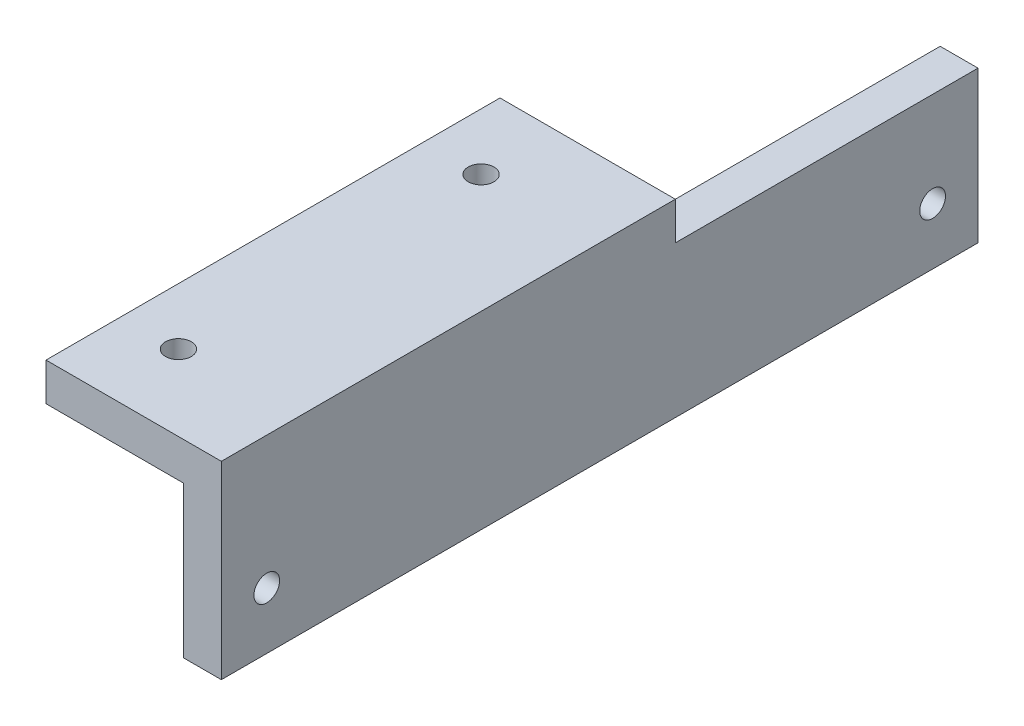
SolidWorks part; units mm, degrees
ref_plane "Front" through (0, 0, 0) normal (0, 0, 1) x (1, 0, 0)
ref_plane "Top" through (0, 0, 0) normal (0, 1, 0) x (1, 0, 0)
ref_plane "Right" through (0, 0, 0) normal (1, 0, 0) x (0, 0, -1)
sketch "Sketch1" plane through (0, 0, 0) normal (1, 0, 0) x (0, 0, -1)
  line L0 (50, 20) -> (50, 0)
  line L1 (0, 0) -> (100, 0)
  line L2 (0, 0) -> (0, 20)
  line L3 (0, 20) -> (100, 20)
  line L4 (100, 0) -> (100, 20)
  line L5 (6, 7.5) -> (94, 7.5)
  line L7 (9.2332, 7.5) -> (7.6166, 10.3)
  line L8 (7.6166, 10.3) -> (4.3834, 10.3)
  line L9 (4.3834, 10.3) -> (2.7668, 7.5)
  line L10 (2.7668, 7.5) -> (4.3834, 4.7)
  line L11 (4.3834, 4.7) -> (7.6166, 4.7)
  line L12 (7.6166, 4.7) -> (9.2332, 7.5)
  line L13 (97.2332, 7.5) -> (95.6166, 10.3)
  line L14 (95.6166, 10.3) -> (92.3834, 10.3)
  line L15 (92.3834, 10.3) -> (90.7668, 7.5)
  line L16 (90.7668, 7.5) -> (92.3834, 4.7)
  line L17 (92.3834, 4.7) -> (95.6166, 4.7)
  line L18 (95.6166, 4.7) -> (97.2332, 7.5)
  circle A0 centre (6, 7.5) radius 1.7
  circle A1 centre (94, 7.5) radius 1.7
  circle A2 centre (6, 7.5) radius 2.8 construction
  circle A3 centre (94, 7.5) radius 2.8 construction
  point P10 (50, 10)
  point P12 (50, 7.5)
  dimension "D4" = 7.5
  dimension "D1" = 20
  dimension "D2" = 100
  dimension "D3" = 88
  dimension "D5" = 0
extrude "Boss-Extrude1" add sketch "Sketch1" along normal blind 2.5 contours A0 L0 L3 L2 L1 | A1 L0 L1 L4 L3 | A0 L7 L8 L9 L10 L11 L12 | A1 L16 L17 L18 L13 L14 L15 region at (0, 8.8572, -91.6492) region at (0, 10.0698, -74.4696) region at (0, 6.1428, -8.3508) region at (0, 10.0698, -25.5304)
extrude "Boss-Extrude2" add sketch "Sketch1<3>" against normal blind 2.5 contours L12 L11 L10 L9 L8 L7 L0 L3 L2 L1 | L18 L17 L16 L0 L1 L4 L3 L15 L14 L13 region at (0, 10.0698, -74.4696) region at (0, 10.0698, -25.5304)
sketch "Sketch1<3>" plane through (0, 0, 0) normal (1, 0, 0) x (0, 0, -1) same geometry as "Sketch1"
sketch "Sketch2" plane through (0, 20, 0) normal (0, 1, 0) x (1, 0, 0)
  line L0 (2.5, 0) -> (2.5, 100)
  line L1 (2.5, 0) -> (-20.675, 0)
  line L2 (2.5, 100) -> (-20.675, 100)
  line L3 (-20.675, 0) -> (-20.675, 100)
  line L4 (-2.5, 0) -> (-2.5, 100) construction
  line L5 (-13.175, 0) -> (-13.175, 100)
  line L6 (-20.675, 15) -> (-2.5, 15)
  line L7 (-13.175, 10) -> (-13.175, 90)
  line L8 (-2.5, 15) -> (2.5, 15)
  line L9 (2.5, 15) -> (2.5, 100)
  line L10 (-20.675, 60) -> (2.5, 60)
  circle A0 centre (-13.175, 10) radius 1.7
  circle A1 centre (-13.175, 90) radius 1.7
  circle A2 centre (-13.175, 50) radius 1.7
  point P15 (-13.175, 50)
  line M7 (-2.5, 100) -> (-2.5, 0)
  line M8 (-2.5, 0) -> (2.5, 0)
  line M9 (2.5, 0) -> (2.5, 100)
  dimension "D6" = 40
  dimension "D7" = 10
  dimension "D1" = 7.5
  dimension "D2" = 18.175
  dimension "D3" = 15
  dimension "D4" = 50
  dimension "D5" = 10
extrude "Boss-Extrude3" add sketch "Sketch2" along normal blind 5 contours A2 L5 L6 L10 M7 | A2 L5 L10 L3 L6 | A0 L7 L6 L3 L1 L5 | A0 L5 L1 L6 L7 M7 | L8 M7 M8 M9 | L10 L8 L0 M7 region at (0, 20, -7.5) region at (0, 20, -37.5) region at (-7.7028, 20, -7.4271) region at (-7.7935, 20, -37.3807) region at (-17.0523, 20, -7.3949) region at (-16.9663, 20, -37.3296)
ref_plane "Plane1" [suppressed] through (2.5, 20, -15) normal (1, 0, 0) x (0, 0, -1)
sketch "Sketch3" [suppressed] plane through (2.5, 20, -15) normal (1, 0, 0) x (0, 0, -1)
  line L0 (0, 0) -> (0, 30)
  line L1 (0, 30) -> (5, 30)
  line L2 (5, 30) -> (5, 0)
  line L3 (5, 0) -> (0, 0)
  dimension "D1" = 30
  dimension "D2" = 5
extrude "Boss-Extrude4" [suppressed] add sketch "Sketch3" against normal up to vertex up to point (-20.675, 20, -15)
fillet "Fillet1" [suppressed] radius 10
sketch "Sketch4" [suppressed] plane through (0, 0, -20) normal (0, 0, -1) x (-1, 0, 0)
  line L0 (13.175, 50) -> (13.175, 30)
  line L1 (20.675, 50) -> (-2.5, 50) construction
  line L2 (-2.5, 30) -> (20.675, 30) construction
  line L3 (20.675, 30) -> (20.675, 50) construction
  circle A0 centre (13.175, 45) radius 1.7
  circle A1 centre (13.175, 35) radius 1.7
  dimension "D4" = 3.4
  dimension "D5" = 3.4
  dimension "D1" = 7.5
  dimension "D2" = 5
  dimension "D3" = 5
extrude "Cut-Extrude1" [suppressed] cut sketch "Sketch4" against normal blind 23 contours L0 A0 | L0 A0 | L0 A1 | L0 A1
